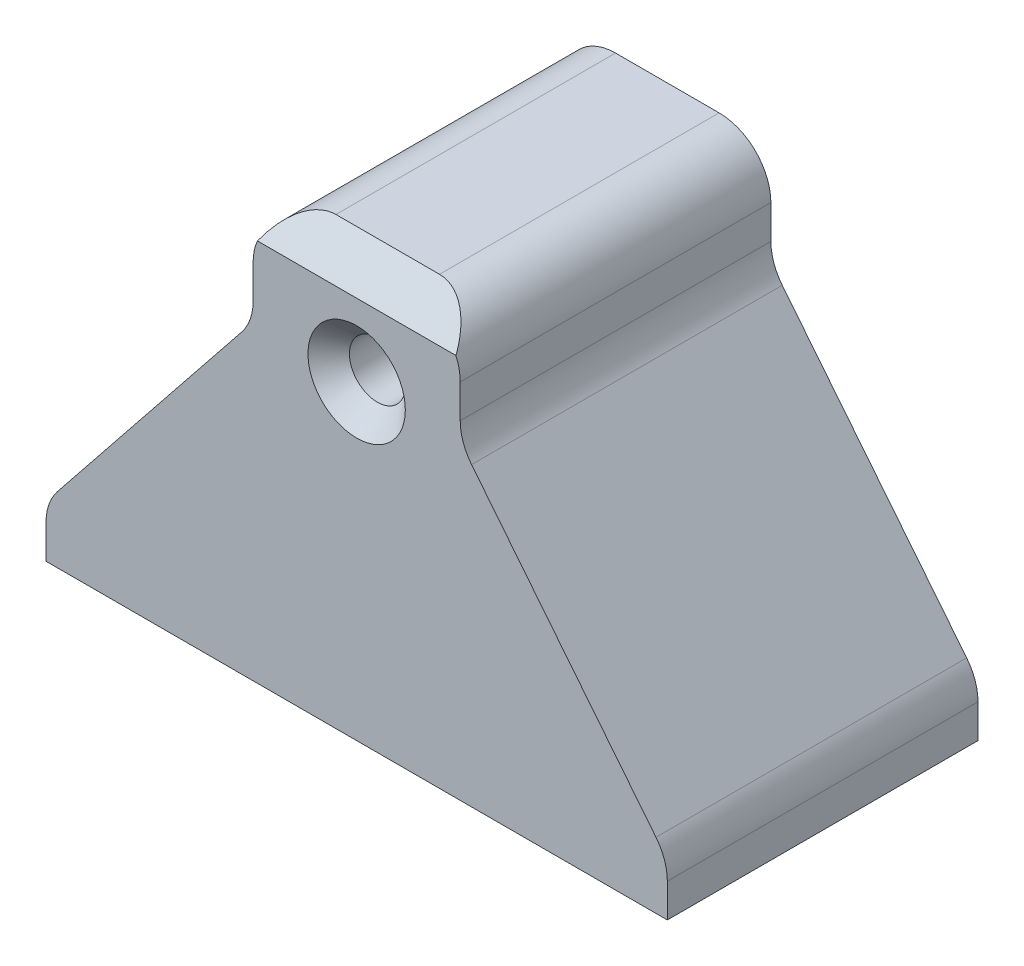
SolidWorks part; units mm, degrees
ref_plane "Front Plane" through (0, 0, 0) normal (0, 0, 1) x (1, 0, 0)
ref_plane "Top Plane" through (0, 0, 0) normal (0, 1, 0) x (1, 0, 0)
ref_plane "Right Plane" through (0, 0, 0) normal (1, 0, 0) x (0, 0, -1)
sketch "Sketch1" plane through (0, 0, 0) normal (0, 0, 1) x (1, 0, 0)
  line L0 (0, 12.7) -> (0, -38.1) construction
  line L1 (-12.7, 12.7) -> (12.7, 12.7)
  line L2 (-12.7, 12.7) -> (-12.7, 0)
  line L3 (38.1, -38.1) -> (-38.1, -38.1)
  line L4 (12.7, 12.7) -> (12.7, 0)
  line L5 (-38.1, -31.75) -> (-12.7, 0)
  line L6 (38.1, -38.1) -> (-38.1, -38.1)
  line L9 (-38.1, -38.1) -> (-38.1, -31.75)
  line L10 (-38.1, -38.1) -> (38.1, -38.1)
  line L11 (38.1, -38.1) -> (38.1, -31.75)
  line L12 (38.1, -31.75) -> (12.7, 0)
  circle A0 centre (0, 0) radius 3.429
  point P7 (0, 12.7)
  dimension "D2" = 6.858
  dimension "D1" = 12.7
  dimension "D3" = 50.8
  dimension "D4" = 25.4
  dimension "D5" = 76.2
  dimension "D6" = 6.35
  dimension "D7" = 38.1
extrude "Boss-Extrude1" add sketch "Sketch1" along normal blind 38.1 contours L0 L1 L2 L5 L9 L10 A0 | L1 L0 A0 L3 L11 L12 L4 region at (14.0207, -18.7722, 0) region at (-14.0207, -18.7722, 0)
sketch "Sketch2" plane through (0, 0, 0) normal (0, 0, -1) x (-1, 0, 0)
  line L1 (6.7458, 0) -> (3.3729, 5.842)
  line L2 (3.3729, 5.842) -> (-3.3729, 5.842)
  line L3 (-3.3729, 5.842) -> (-6.7458, 0)
  line L4 (-6.7458, 0) -> (-3.3729, -5.842)
  line L5 (-3.3729, -5.842) -> (3.3729, -5.842)
  line L6 (3.3729, -5.842) -> (6.7458, 0)
  circle A0 centre (0, 0) radius 5.842 construction
  dimension "D1" = 11.684
extrude "Cut-Extrude1" cut sketch "Sketch2" against normal offset from surface (19.05 mm away) 19.05 up to face at (3.429, 0, 38.1)
chamfer "Chamfer1" distance 2.54 angle 45 6 edges at (0, 5.842, 0) (-5.0593, 2.921, 0) (-5.0593, -2.921, 0) (0, -5.842, 0) (5.0593, -2.921, 0) (5.0593, 2.921, 0)
chamfer "Chamfer2" distance 2.54 angle 45 1 edges at (3.429, 0, 38.1)
fillet "Fillet1" radius 6.35 6 edges at (-38.1, -31.75, 19.05) (-12.7, 0, 19.05) (-12.7, 12.7, 19.05) (12.7, 12.7, 19.05) (38.1, -31.75, 19.05) (12.7, 0, 19.05)
chamfer "Chamfer3" distance 3.81 angle 45 1 edges at (0, 12.7, 38.1) tangent propagation no
